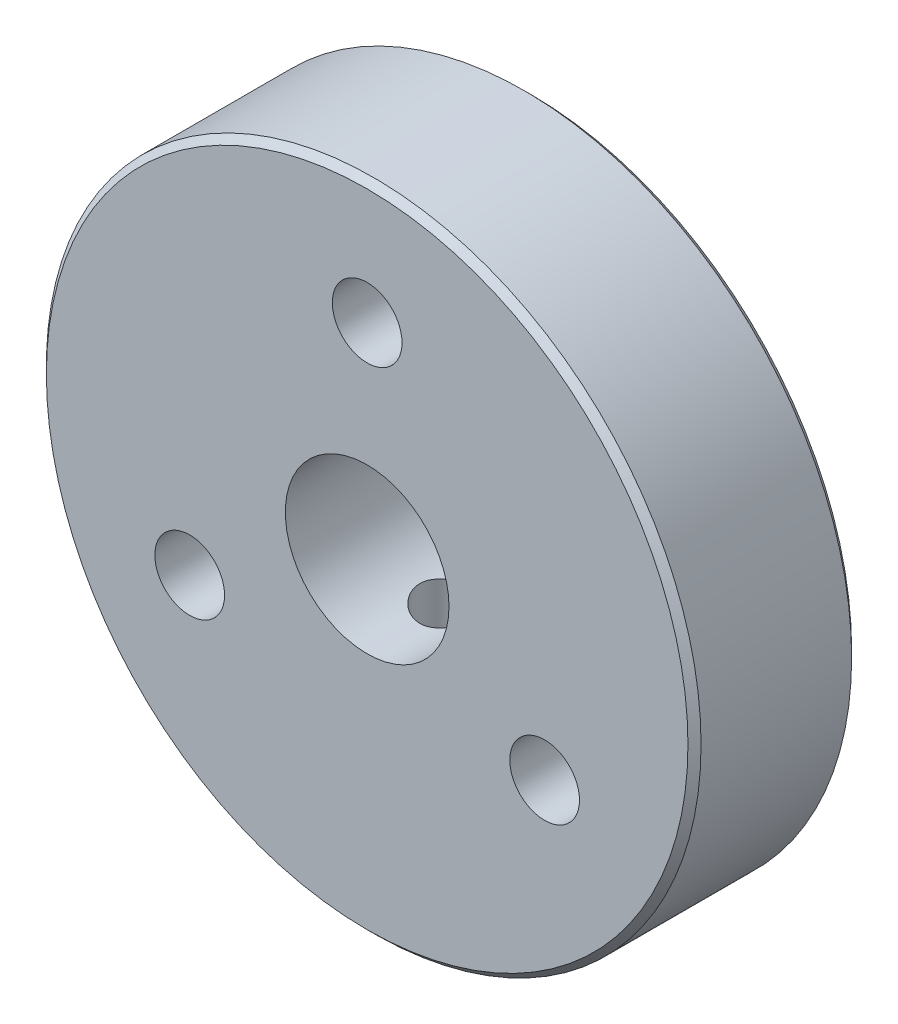
SolidWorks part; units mm, degrees
material "6061-T6 (SS)"
ref_plane "Front Plane" through (0, 0, 0) normal (0, 0, 1) x (1, 0, 0)
ref_plane "Top Plane" through (0, 0, 0) normal (0, 1, 0) x (1, 0, 0)
ref_plane "Right Plane" through (0, 0, 0) normal (1, 0, 0) x (0, 0, -1)
sketch "Sketch2" plane through (0, 0, 0) normal (0, 0, 1) x (1, 0, 0)
  circle A0 centre (0, 0) radius 12.7
  circle A1 centre (0, 0) radius 3.175
  dimension "D1" = 25.4
  dimension "D2" = 6.35
  dimension "D3" = 9.525
extrude "Boss-Extrude1" add sketch "Sketch2" along normal mid plane 6.35
chamfer "Chamfer1" distance 0.254 angle 45 2 edges at (12.7, 0, -3.175) (12.7, 0, 3.175)
hole_wizard "#6-32 Tapped Hole1" positions "Sketch3" profile "Sketch4" tap size "#6-32" standard "ANSI Inch" end condition through all
sketch "Sketch3" plane through (0, 0, 3.175) normal (0, 0, 1) x (1, 0, 0)
  line L0 (0, 0) -> (0, 7.9502) construction
  line L3 (3.4925, 0) -> (-3.4925, 0) construction
  circle A2 centre (0, 0) radius 7.9502 construction
  point P0 (0, 7.9502)
  point P9 (6.8851, -3.9751)
  point P10 (-6.8851, -3.9751)
  dimension "D1" = 7.9502
  dimension "D3" = 90
  dimension "D2" = 3
sketch "Sketch4" plane through (0, 7.9502, 3.175) normal (1, 0, 0) x (0, -1, 0)
  line L0 (0, 0) -> (0, 6.35)
  line L1 (0, 6.35) -> (1.3525, 6.35)
  line L2 (1.3525, 6.35) -> (1.3525, 0)
  line L5 (1.3525, 0) -> (0, 0)
  line L11 (0, -6.35) -> (0, 107.95) construction
  dimension "Thru Tap Drill Dia." = 2.7051
  dimension "Thru Tap Drill Depth" = 6.35
cosmetic thread "Hole Thread4"
cosmetic thread "Hole Thread5"
cosmetic thread "Hole Thread6"
ref_plane "Plane1" through (0, -12.7, 0) normal (0, -1, 0) x (-1, 0, 0)
hole_wizard "#4-40 Tapped Hole2" positions "Sketch9" profile "Sketch10" tap size "#4-40" standard "ANSI Inch" end condition up to next
sketch "Sketch9" plane through (0, -12.7, 0) normal (0, -1, 0) x (-1, 0, 0)
  point P0 (0, 0)
sketch "Sketch10" plane through (0, -12.7, 0) normal (1, 0, 0) x (0, 0, -1)
  line L0 (0, 0) -> (0, 9.525)
  line L1 (0, 9.525) -> (1.1303, 9.525)
  line L2 (1.1303, 9.525) -> (1.1303, 0.3945)
  line L3 (1.1303, 0.3945) -> (1.4732, 0)
  line L5 (1.4732, 0) -> (0, 0)
  line L6 (-1.1303, 0.3945) -> (-1.4732, 0) construction
  line L11 (0, -6.35) -> (0, 107.95) construction
  dimension "Thru Tap Drill Dia." = 2.2606
  dimension "Thru Tap Drill Depth" = 9.525
  dimension "Near C'Sink Dia." = 2.9464
  dimension "Near C'Sink Angle" = 82
cosmetic thread "Hole Thread3"
